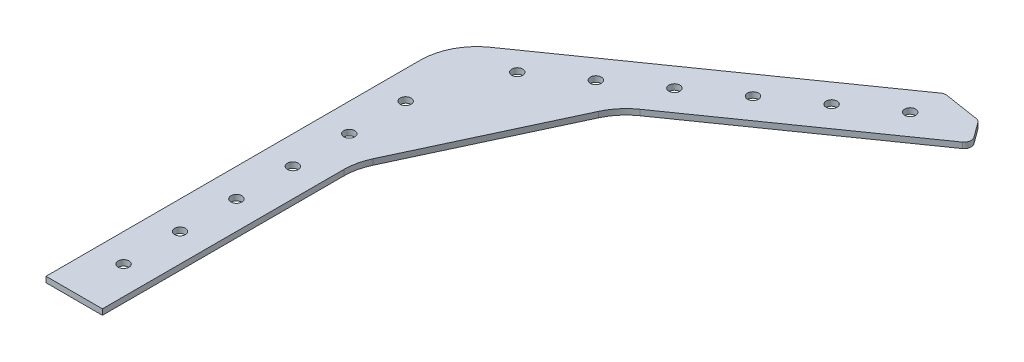
SolidWorks part; units mm, degrees
material "6061-T6 (SS)"
ref_plane "Front Plane" through (0, 0, 0) normal (0, 0, 1) x (1, 0, 0)
ref_plane "Top Plane" through (0, 0, 0) normal (0, 1, 0) x (1, 0, 0)
ref_plane "Right Plane" through (0, 0, 0) normal (1, 0, 0) x (0, 0, -1)
sketch "Sketch1" plane through (0, 0, 0) normal (0, 1, 0) x (1, 0, 0)
  line L0 (-49.1325, -114.0724) -> (-23.7325, -114.0724)
  line L1 (-23.7325, -114.0724) -> (-23.7325, 0.2276)
  line L2 (-23.7325, 0.2276) -> (13.8383, 80.7984)
  line L3 (13.8383, 80.7984) -> (107.4674, 146.3582)
  line L4 (92.4976, 166.8781) -> (107.4674, 146.3582)
  line L5 (-49.1325, -114.0724) -> (-49.1325, 67.7076)
  line L6 (-49.1325, 67.7076) -> (92.4976, 166.8781)
  dimension "D1" = 25.4
  dimension "D2" = 114.3
  dimension "D3" = 150
  dimension "D4" = 88.9
  dimension "D5" = 114.3
  dimension "D6" = 155
  dimension "D7" = 25.4
  dimension "D8" = 150
extrude "Boss-Extrude1" add sketch "Sketch1" along normal mid plane 2.54 contours L2 L3 L4 L6 L5 L0 L1
sketch "Sketch2" plane through (0, 1.27, 0) normal (0, 1, 0) x (1, 0, 0)
  line L0 (-49.1325, -114.0724) -> (-23.7325, -114.0724) construction
  line L4 (-23.7325, -114.0724) -> (-23.7325, 0.2276) construction
  point P0 (-36.4325, -91.8474)
  point P7 (-36.4325, -66.4474)
  point P8 (-36.4325, -41.0474)
  point P9 (-36.4325, -15.6474)
  point P10 (-36.4325, 9.7526)
  point P11 (-36.4325, 35.1526)
  dimension "D1" = 22.225
  dimension "D2" = 12.7
  dimension "D3" = 6
sketch "Sketch6" plane through (0, 1.27, 0) normal (0, 1, 0) x (1, 0, 0)
  line L0 (92.4976, 166.8781) -> (107.4674, 146.3582) construction
  line L1 (-49.1325, 67.7076) -> (92.4976, 166.8781) construction
  point P0 (81.4136, 144.4055)
  point P1 (99.9825, 156.6181)
  point P8 (60.6071, 129.8367)
  point P9 (39.8007, 115.2679)
  point P10 (18.9942, 100.699)
  point P11 (-1.8123, 86.1302)
  point P12 (-22.6187, 71.5613)
  dimension "D1" = 22.225
  dimension "D2" = 12.0509
  dimension "D3" = 6
hole_wizard "#10 (0.1935) Diameter Hole2" positions "Sketch8" profile "Sketch7" hole size "#10" standard "ANSI Inch"
sketch "Sketch8" plane through (0, 1.27, 0) normal (0, 1, 0) x (1, 0, 0)
  point P0 (81.4136, 144.4055)
  point P3 (60.6071, 129.8367)
  point P6 (39.8007, 115.2679)
  point P9 (18.9942, 100.699)
  point P12 (-1.8123, 86.1302)
  point P15 (-22.6187, 71.5613)
  point P18 (-36.4325, 35.1526)
  point P21 (-36.4325, 9.7526)
  point P24 (-36.4325, -15.6474)
  point P27 (-36.4325, -41.0474)
  point P30 (-36.4325, -66.4474)
  point P33 (-36.4325, -91.8474)
sketch "Sketch7" plane through (81.4136, 1.27, -144.4055) normal (1, 0, 0) x (0, 0, 1)
  line L0 (0, 0) -> (0, 52.2766)
  line L1 (0, 52.2766) -> (2.4574, 50.8)
  line L2 (2.4574, 50.8) -> (2.4574, 0)
  line L5 (2.4574, 0) -> (0, 0)
  line L10 (0, 52.2766) -> (-2.4575, 50.8) construction
  line L11 (0, -6.35) -> (0, 107.95) construction
  dimension "Hole Dia." = 4.9149
  dimension "Hole Depth" = 50.8
  dimension "Drill Angle" = 118
fillet "Fillet1" radius 25.4 3 edges at (-49.1325, 0, -67.7076) (13.8383, 0, -80.7984) (-23.7325, 0, -0.2276)
chamfer "Chamfer1" distance 12.7 angle 45 1 edges at (92.4976, 0, -166.8781) first distance on face at (99.9825, 0, -156.6181)
fillet "Fillet3" radius 3.175 3 edges at (107.4674, 0, -146.3582) (99.9825, 0, -156.6181) (81.8865, 0, -159.4481)
